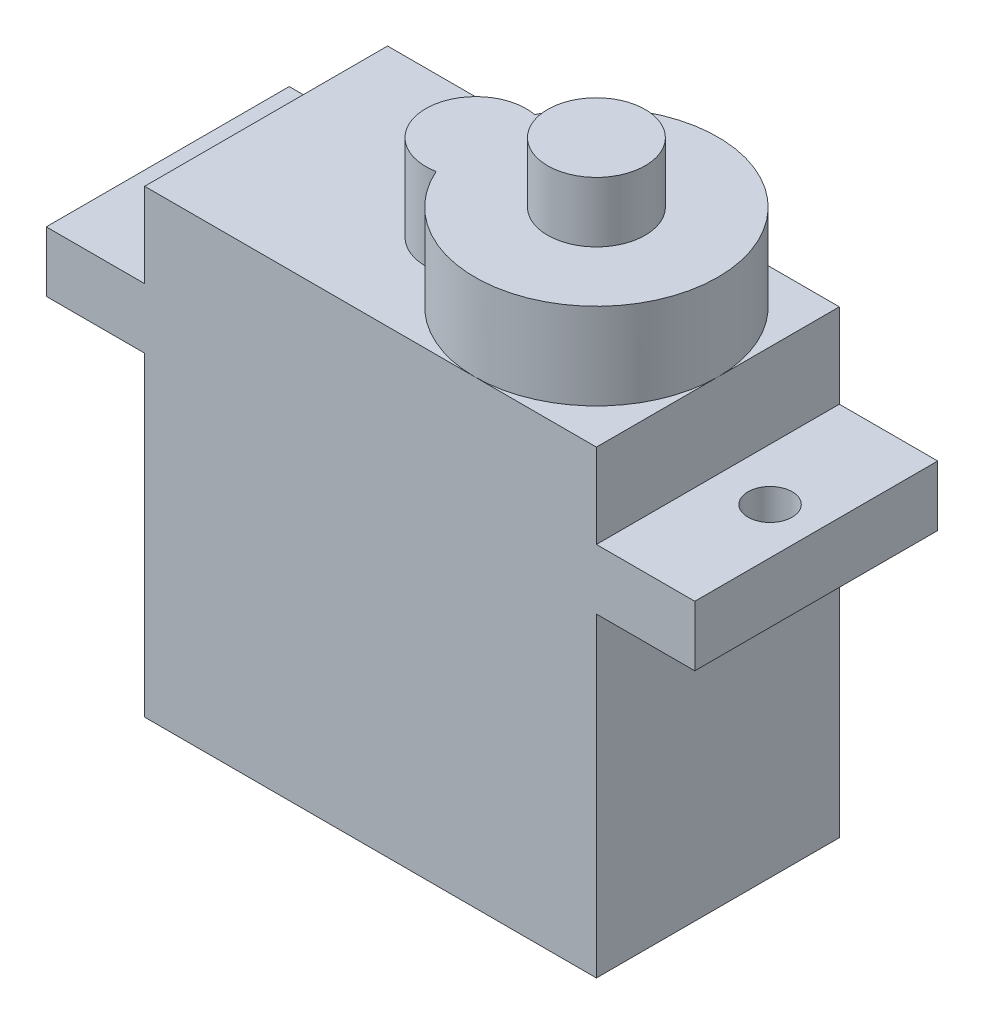
SolidWorks part; units mm, degrees
ref_plane "Front Plane" through (0, 0, 0) normal (0, 0, 1) x (1, 0, 0)
ref_plane "Top Plane" through (0, 0, 0) normal (0, 1, 0) x (1, 0, 0)
ref_plane "Right Plane" through (0, 0, 0) normal (1, 0, 0) x (0, 0, -1)
sketch "Sketch1" plane through (0, 0, 0) normal (0, 1, 0) x (1, 0, 0)
  line L1 (0, 0) -> (22.5, 0)
  line L2 (0, 0) -> (0, 12.1)
  line L3 (0, 12.1) -> (22.5, 12.1)
  line L4 (22.5, 0) -> (22.5, 12.1)
  dimension "D1" = 22.5
  dimension "D2" = 12.1
extrude "Boss-Extrude1" add sketch "Sketch1" along normal blind 15.7
sketch "Sketch2" plane through (0, 15.7, 0) normal (0, 1, 0) x (1, 0, 0)
  line L0 (0, 0) -> (22.5, 0) construction
  line L1 (-4.9, 12.1) -> (27.4, 12.1)
  line L2 (-4.9, 12.1) -> (-4.9, 0)
  line L3 (-4.9, 0) -> (27.4, 0)
  line L4 (27.4, 12.1) -> (27.4, 0)
  line L5 (22.5, 12.1) -> (0, 12.1) construction
  line L7 (22.5, 12.1) -> (0, 12.1) construction
  point P8 (11.25, 12.1)
  dimension "D1" = 32.3
extrude "Boss-Extrude2" add sketch "Sketch2" along normal blind 3
extrude "Boss-Extrude3" add sketch "Sketch1<2>" along normal blind 4.2 from surface starting at face at (11.25, 18.7, -6.05)
sketch "Sketch1<2>" plane through (0, 0, 0) normal (0, 1, 0) x (1, 0, 0) same geometry as "Sketch1"
sketch "Sketch3" plane through (0, 22.9, 0) normal (0, 1, 0) x (1, 0, 0)
  line L0 (0, 6.05) -> (22.5, 6.05) construction
  line L1 (0, 0) -> (0, 12.1) construction
  line L2 (22.5, 12.1) -> (22.5, 0) construction
  line L3 (0, 12.1) -> (22.5, 12.1) construction
  circle A0 centre (16.45, 6.05) radius 6.05
  circle A1 centre (10.45, 6.05) radius 2.5
  dimension "D1" = 6
  dimension "D2" = 5
extrude "Boss-Extrude4" add sketch "Sketch3" along normal blind 4.3 contours L0 A1 A0 | A1 L0 A0 | L0 A0 A1 | A0 L0 A1 | A1 L0 A0 | L0 A1 A0 region at (16.8741, 22.9, -8.7549) region at (11.5717, 22.9, -5.0603) region at (11.5717, 22.9, -7.0397) region at (16.8741, 22.9, -3.3451) region at (9.4614, 22.9, -4.9261) region at (9.4614, 22.9, -7.1739)
sketch "Sketch4" plane through (0, 27.2, 0) normal (0, 1, 0) x (1, 0, 0)
  circle A0 centre (16.45, 6.05) radius 2.43
  arc A1 (22.5, 6.05) -> (16.45, 12.1) centre (16.45, 6.05) ccw construction
  point P2 (0, 0)
  dimension "D1" = 4.86
extrude "Boss-Extrude5" add sketch "Sketch4" along normal blind 3
sketch "Sketch5" plane through (0, 18.7, 0) normal (0, 1, 0) x (1, 0, 0)
  line L0 (-2.6, 6.05) -> (25.1, 6.05) construction
  line L3 (0, 0) -> (22.5, 0) construction
  line L4 (0, 0) -> (22.5, 0) construction
  line L5 (11.25, 0) -> (11.25, 12.1) construction
  line L6 (0, 12.1) -> (16.45, 12.1) construction
  circle A0 centre (-2.6, 6.05) radius 1.1
  circle A1 centre (25.1, 6.05) radius 1.1
  point P10 (11.25, 6.05)
  dimension "D1" = 2.2
  dimension "D2" = 2.2
  dimension "D3" = 27.7
extrude "Cut-Extrude1" cut sketch "Sketch5" against normal blind 3
